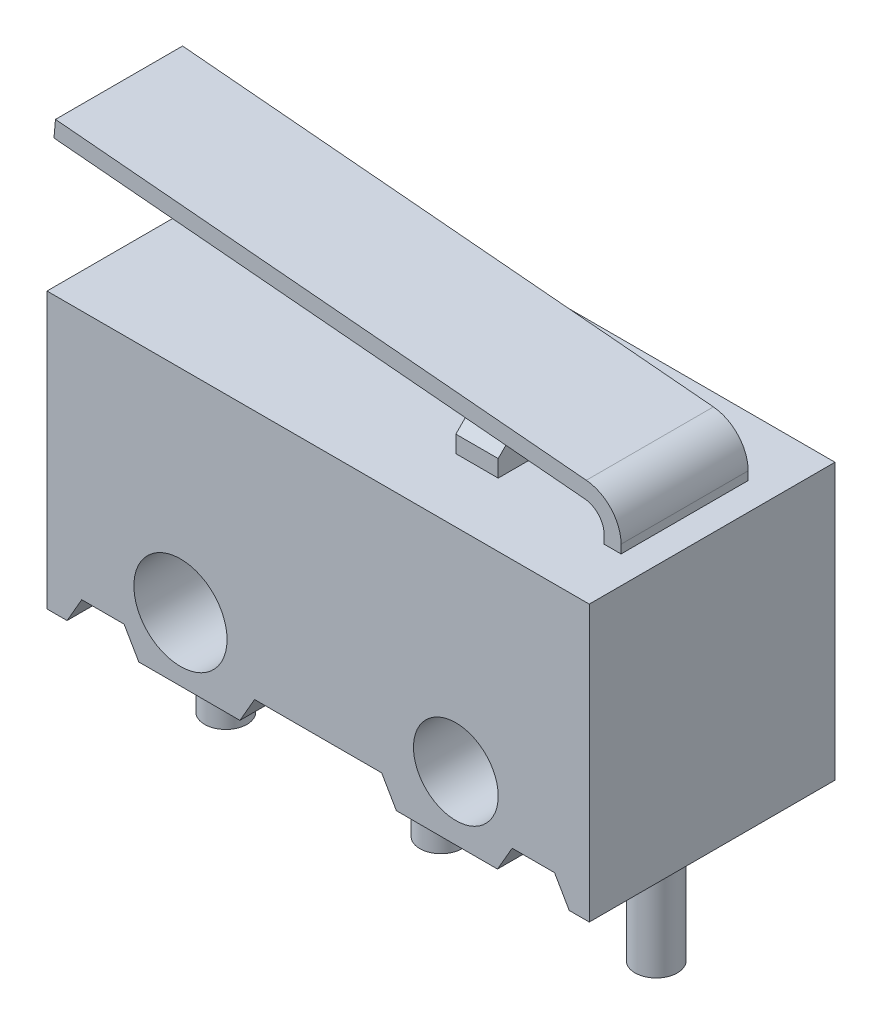
SolidWorks part; units mm, degrees
ref_plane "Front Plane" through (0, 0, 0) normal (0, 0, 1) x (1, 0, 0)
ref_plane "Top Plane" through (0, 0, 0) normal (0, 1, 0) x (1, 0, 0)
ref_plane "Right Plane" through (0, 0, 0) normal (1, 0, 0) x (0, 0, -1)
sketch "Sketch1" plane through (0, 0, 0) normal (0, 0, 1) x (1, 0, 0)
  line L0 (-6.4, 0) -> (6.4, 0) construction
  line L2 (0, 0) -> (0, 5) construction
  line L3 (0, -3.3) -> (0, 3.3) construction
  line L5 (-6.4, 5) -> (6.4, 5)
  line L6 (-6.4, 5) -> (-6.4, -1.5)
  line L7 (-6.4, -1.5) -> (6.4, -1.5)
  line L8 (6.4, 5) -> (6.4, -1.5)
  circle A0 centre (-3.25, 0) radius 1.1
  circle A1 centre (3.25, 0) radius 1
  dimension "D3" = 1.5
  dimension "D5" = 2
  dimension "D6" = 2.2
  dimension "D1" = 5
  dimension "D2" = 12.8
  dimension "D4" = 6.5
extrude "Boss-Extrude1" add sketch "Sketch1" along normal mid plane 5.8
sketch "Sketch12" plane through (0, 0, 2.9) normal (0, 0, 1) x (1, 0, 0)
  line L0 (-1.8464, -1.5) -> (-1.5, -0.9)
  line L1 (-6.4, -1.5) -> (6.4, -1.5) construction
  line L2 (-1.5, -0.9) -> (1.5, -0.9)
  line L3 (1.5, -0.9) -> (1.8464, -1.5)
  line L4 (1.8464, -1.5) -> (-1.8464, -1.5)
  line L5 (-5.9264, -1.5) -> (-5.58, -0.9)
  line L6 (-5.58, -0.9) -> (-4.58, -0.9)
  line L7 (-4.58, -0.9) -> (-4.2336, -1.5)
  line L8 (-4.2336, -1.5) -> (-5.9264, -1.5)
  line L9 (0, -0.9) -> (0, -1.5) construction
  line L10 (-5.08, -0.9) -> (-5.08, -1.5) construction
  line L11 (5.08, -0.9) -> (5.08, -1.5) construction
  line L12 (4.2336, -1.5) -> (5.9264, -1.5)
  line L13 (4.58, -0.9) -> (4.2336, -1.5)
  line L14 (5.58, -0.9) -> (4.58, -0.9)
  line L15 (5.9264, -1.5) -> (5.58, -0.9)
  dimension "D1" = 0.6
  dimension "D2" = 60
  dimension "D3" = 5.08
  dimension "D4" = 1
  dimension "D5" = 3
extrude "Cut-Extrude4" cut sketch "Sketch12" against normal through all
sketch "Sketch3" plane through (0, 0, 0) normal (0, 0, 1) x (1, 0, 0)
  line L1 (1.75, 5.9) -> (2.75, 5.9)
  line L2 (1.75, 5.9) -> (1.75, 5)
  line L3 (1.75, 5) -> (2.75, 5)
  line L4 (2.75, 5.9) -> (2.75, 5)
  line L7 (6.4, 5) -> (-6.4, 5) construction
  line L8 (2.25, 5.9) -> (2.25, 5) construction
  circle A0 centre (3.25, 0) radius 1 construction
  dimension "D1" = 1
  dimension "D2" = 5.9
extrude "Boss-Extrude2" add sketch "Sketch3" along normal mid plane 2.8
chamfer "Chamfer1" distance 0.5 angle 45 2 edges at (2.25, 5.9, -1.4) (2.25, 5.9, 1.4)
sketch "Sketch13" plane through (0, -0.9, 0) normal (0, -1, 0) x (1, 0, 0)
  line L0 (-1000, 0) -> (49000, 0) construction
  circle A0 centre (0, 0) radius 0.5
  circle A1 centre (-5.08, 0) radius 0.5
  circle A2 centre (5.08, 0) radius 0.5
  dimension "D2" = 5.08
  dimension "D3" = 1
  dimension "D4" = 1
  dimension "D5" = 1
  dimension "D1" = 5.08
extrude "Boss-Extrude9" add sketch "Sketch13" along normal blind 3.5
sketch "Sketch6" plane through (0, 0, 0) normal (0, 0, 1) x (1, 0, 0)
  line L0 (1.5, -0.9) -> (-1.5, -0.9) construction
  line L2 (-0.45, -0.9) -> (0.45, -0.9)
  line L3 (-0.45, -0.9) -> (-0.45, -4.4)
  line L4 (-0.45, -4.4) -> (0.45, -4.4)
  line L5 (0.45, -0.9) -> (0.45, -4.4)
  line L6 (-4.58, -0.9) -> (-5.58, -0.9) construction
  line L7 (0, 0) -> (0, -14.9776) construction
  line L8 (0, -3.19) -> (0, 3.19) construction
  line L10 (-5.53, -0.9) -> (-4.63, -0.9)
  line L12 (-5.53, -0.9) -> (-5.53, -4.4)
  line L13 (-5.53, -4.4) -> (-4.63, -4.4)
  line L14 (-4.63, -0.9) -> (-4.63, -4.4)
  line L16 (-5.08, -0.9) -> (-5.08, -4.4) construction
  line L17 (5.08, -0.9) -> (5.08, -4.4) construction
  line L18 (4.63, -0.9) -> (4.63, -4.4)
  line L19 (5.53, -4.4) -> (4.63, -4.4)
  line L20 (5.53, -0.9) -> (5.53, -4.4)
  line L21 (5.53, -0.9) -> (4.63, -0.9)
  dimension "D1" = 0.9
  dimension "D2" = 3.5
  dimension "D3" = 5.08
sketch "Sketch11" plane through (0, 0, 0) normal (0, 0, 1) x (1, 0, 0)
  line L0 (-7.6354, 6.81) -> (4.8944, 5.698)
  line L1 (-7.6, 7.2084) -> (4.9297, 6.0965)
  line L2 (5.3502, 5.2) -> (5.3502, 5)
  line L3 (6.4, 5) -> (-6.4, 5) construction
  line L4 (-7.6, 7.2084) -> (-7.6354, 6.81)
  line L5 (-19.9556, 7.9034) -> (4.8944, 5.698) construction
  line L6 (-19.5372, 8.2678) -> (4.9297, 6.0965) construction
  line L7 (5.3502, 5) -> (5.7502, 5)
  line L8 (5.7502, 5.2) -> (5.7502, 5)
  line L9 (6.4, -1.5) -> (6.4, 5) construction
  line L10 (6.4, 5) -> (-6.4, 5) construction
  line L11 (5.7502, 5.2) -> (5.7502, 5) construction
  arc A2 (4.8944, 5.698) -> (5.3502, 5.2) centre (4.8502, 5.2) cw
  arc A6 (4.9297, 6.0965) -> (5.7502, 5.2) centre (4.8502, 5.2) cw
  arc A7 (-17.3682, 4.6852) -> (-20.806, 8.4391) centre (-16.5768, 8.8611) ccw construction
  arc A9 (-17.3682, 4.6852) -> (-19.5372, 8.2678) centre (-16.0827, 7.9114) ccw construction
  arc A10 (-19.7593, 6.694) -> (-19.9556, 7.9034) centre (-16.0827, 7.9114) ccw construction
  arc A11 (-19.7593, 6.694) -> (-20.408, 8.4789) centre (-16.5768, 8.8611) ccw construction
  point P15 (5.3502, 5.6576)
  point P31 (-3.25, 0)
  dimension "D1" = 0.6498
  dimension "D4" = 0.4
  dimension "D3" = 0.5
  dimension "D5" = 6.81
  dimension "D6" = 4.35
  dimension "D2" = 0.2
extrude "Boss-Extrude8" add sketch "Sketch11" along normal mid plane 3 separate body
